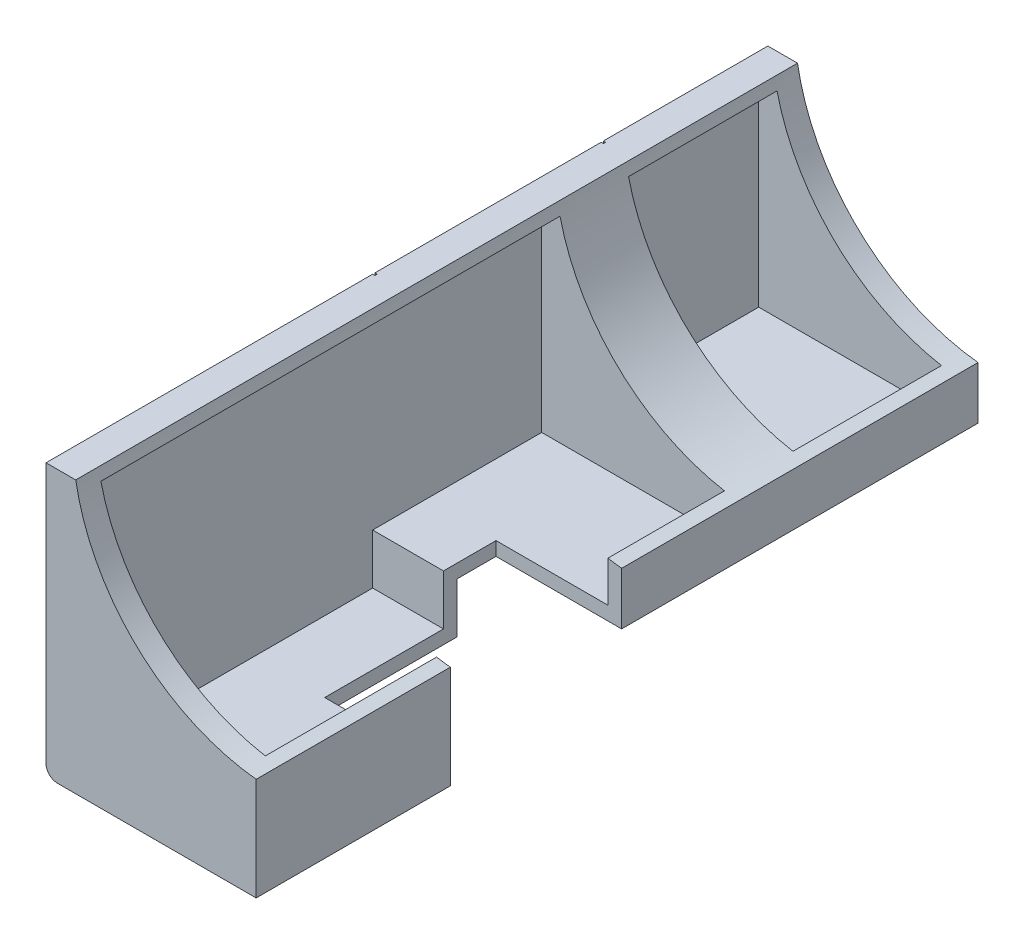
SolidWorks part; units mm, degrees
material "Acrylic (Medium-high impact)"
ref_plane "Front Plane" through (0, 0, 0) normal (0, 0, 1) x (1, 0, 0)
ref_plane "Top Plane" through (0, 0, 0) normal (0, 1, 0) x (1, 0, 0)
ref_plane "Right Plane" through (0, 0, 0) normal (1, 0, 0) x (0, 0, -1)
sketch "Sketch2" plane through (0, 0, 0) normal (0, 0, 1) x (1, 0, 0)
  line L0 (-0.9659, -13.448) -> (-0.9659, -8.948)
  line L1 (-8.8659, -1.548) -> (-10.1659, -1.548)
  line L2 (-10.1659, -1.548) -> (-10.1659, -13.448)
  line L3 (-10.1659, -13.448) -> (-0.9659, -13.448)
  arc A0 (-8.8659, -1.548) -> (-0.9659, -8.948) centre (0, 0) ccw
  dimension "D1" = 11.9
  dimension "D5" = 18
  dimension "D2" = 1.3
  dimension "D3" = 4.5
  dimension "D4" = 9.2
extrude "Boss-Extrude1" add sketch "Sketch2" against normal blind 31.6 contours L2 L3 L0 A0 L1
sketch "Sketch4" plane through (-10.1659, 0, 0) normal (-1, 0, 0) x (0, 0, 1)
  line L1 (-13.5, -12.248) -> (-0.8, -12.248)
  line L2 (-13.5, -12.248) -> (-13.5, -2.248)
  line L3 (-13.5, -2.248) -> (-0.8, -2.248)
  line L4 (-0.8, -12.248) -> (-0.8, -2.248)
  line L6 (-31.6, -1.548) -> (0, -1.548) construction
  line L8 (-23.5, -2.248) -> (-15.2, -2.248)
  line L9 (-23.5, -2.248) -> (-23.5, -10.048)
  line L10 (-23.5, -10.048) -> (-15.2, -10.048)
  line L11 (-15.2, -2.248) -> (-15.2, -10.048)
  line L12 (-31, -2.248) -> (-25.2, -2.248)
  line L13 (-31, -2.248) -> (-31, -9.848)
  line L14 (-31, -9.848) -> (-25.2, -9.848)
  line L15 (-25.2, -2.248) -> (-25.2, -9.848)
  line L16 (0, -1.548) -> (0, -13.448) construction
  dimension "D1" = 10
  dimension "D2" = 12.7
  dimension "D3" = 0.7
  dimension "D4" = 10.7
  dimension "D5" = 7.8
  dimension "D6" = 5.8
  dimension "D7" = 8.3
  dimension "D8" = 7.6
  dimension "D9" = 1.7
  dimension "D10" = 1.7
  dimension "D11" = 13.5
extrude "Boss-Extrude2" add sketch "Sketch4" along normal blind 0.35
fillet "Fillet1" radius 0.5 12 edges at (-10.3409, -10.048, -23.5) (-10.3409, -10.048, -15.2) (-10.3409, -2.248, -15.2) (-10.3409, -2.248, -23.5) (-10.3409, -12.248, -13.5) (-10.3409, -12.248, -0.8) (-10.3409, -2.248, -0.8) (-10.3409, -2.248, -13.5) (-10.3409, -9.848, -25.2) (-10.3409, -2.248, -31) (-10.3409, -9.848, -31) (-10.3409, -2.248, -25.2)
sketch "Sketch5" plane through (-10.5159, 0, 0) normal (-1, 0, 0) x (0, 0, 1)
  circle A0 centre (-13, -2.748) radius 0.25
  circle A1 centre (-1.3, -2.748) radius 0.25
  circle A2 centre (-23, -2.748) radius 0.25
  circle A3 centre (-23, -9.548) radius 0.25
  circle A4 centre (-1.3, -11.748) radius 0.25
  circle A5 centre (-13, -11.748) radius 0.25
  circle A6 centre (-15.7, -2.748) radius 0.25
  circle A7 centre (-15.7, -9.548) radius 0.25
  circle A8 centre (-30.5, -2.748) radius 0.25
  circle A9 centre (-25.7, -2.748) radius 0.25
  circle A10 centre (-25.7, -9.348) radius 0.25
  circle A11 centre (-30.5, -9.348) radius 0.25
  dimension "D1" = 0.5
extrude "Boss-Extrude3" add sketch "Sketch5" along normal blind 0.1
sketch "Sketch19" plane through (-10.1659, 0, 0) normal (-1, 0, 0) x (0, 0, 1)
  line L0 (-31.6, -1.548) -> (0, -1.548) construction
  line L1 (-31.6, -13.448) -> (-14.3, -13.448)
  line L2 (-31.6, -13.448) -> (-31.6, -11.248)
  line L3 (-31.6, -11.248) -> (-14.3, -11.248)
  line L4 (-14.3, -13.448) -> (-14.3, -11.248)
  line L5 (0, -1.548) -> (0, -13.448) construction
  dimension "D1" = 9.7
  dimension "D2" = 14.3
extrude "Cut-Extrude11" cut sketch "Sketch19" against normal through all
fillet "Fillet2" radius 0.5 2 edges at (-10.1659, -11.248, -22.95) (-10.1659, -13.448, -7.15)
sketch "Sketch21" plane through (-10.1659, 0, 0) normal (-1, 0, 0) x (0, 0, 1)
  line L0 (-31.6, -1.548) -> (0, -1.548) construction
  line L1 (-14.3, -11.248) -> (-14.4, -11.248)
  line L2 (-14.3, -11.248) -> (-14.3, -1.548)
  line L3 (-14.3, -1.548) -> (-14.4, -1.548)
  line L4 (-14.4, -11.248) -> (-14.4, -1.548)
  line L5 (-14.3, -11.248) -> (-31.6, -11.248) construction
  line L6 (-24.35, -1.548) -> (-24.35, -11.248) construction
  line L7 (-25.2, -9.348) -> (-25.2, -2.748) construction
  line L8 (-23.5, -2.748) -> (-23.5, -9.548) construction
  line L10 (-24.3, -11.248) -> (-24.4, -11.248)
  line L11 (-24.3, -11.248) -> (-24.3, -1.548)
  line L12 (-24.3, -1.548) -> (-24.4, -1.548)
  line L13 (-24.4, -11.248) -> (-24.4, -1.548)
  dimension "D1" = 0.1
  dimension "D2" = 0.1
extrude "Cut-Extrude13" cut sketch "Sketch21" against normal blind 0.1
sketch "Sketch20" plane through (0, 0, 0) normal (0, 1, 0) x (1, 0, 0)
  line L0 (-0.9659, 31.6) -> (-0.9659, 0) construction
  line L1 (-0.9659, 8.5) -> (-6.4659, 8.5)
  line L2 (-0.9659, 8.5) -> (-0.9659, 16)
  line L3 (-0.9659, 16) -> (-6.4659, 16)
  line L4 (-6.4659, 8.5) -> (-6.4659, 16)
  line L5 (-8.8659, 0) -> (-0.9659, 0) construction
  line L6 (-10.5159, 1.3) -> (-10.5159, 13) construction
  dimension "D1" = 7.5
  dimension "D2" = 8.5
  dimension "D3" = 4.05
  dimension "D4" = 5.5
extrude "Cut-Extrude12" cut sketch "Sketch20" against normal through all
sketch "Sketch22" plane through (0, -1.548, 0) normal (0, 1, 0) x (1, 0, 0)
  line L0 (-8.8659, 31.6) -> (-8.8659, 0) construction
  line L1 (-8.8659, 1) -> (-1.5659, 1)
  line L2 (-8.8659, 1) -> (-8.8659, 21.1)
  line L3 (-8.8659, 13.7) -> (-1.5659, 13.7)
  line L4 (-1.5659, 1) -> (-1.5659, 21.1)
  line L5 (-6.4659, 14.3) -> (-9.6659, 14.3) construction
  line L6 (-8.8659, 21.1) -> (-1.5659, 21.1)
  line L8 (-8.8659, 0) -> (-0.9659, 0) construction
  line L9 (-1.5659, 24.1) -> (-8.8659, 24.1)
  line L10 (-1.5659, 24.1) -> (-1.5659, 30.6)
  line L11 (-1.5659, 30.6) -> (-8.8659, 30.6)
  line L12 (-8.8659, 24.1) -> (-8.8659, 30.6)
  line L13 (-0.9659, 31.6) -> (-8.8659, 31.6) construction
  line L14 (-0.9659, 31.6) -> (-0.9659, 16) construction
  line M9 (-8.8659, 0) -> (-8.8659, 31.6)
  dimension "D1" = 1
  dimension "D2" = 1
  dimension "D3" = 0.6
  dimension "D4" = 6.5
  dimension "D5" = 3
  dimension "D6" = 0.6
extrude "Cut-Extrude14" cut sketch "Sketch22" against normal offset from surface (11.3 mm away) 0.6 contours L1 L4 L3 M9 region at (-5.2159, -1.548, -7.35) up to face at (-5.6992, -13.448, -7.6)
extrude "Cut-Extrude15" cut sketch "Sketch22<3>" against normal offset from surface (9.1 mm away) 0.6 contours L6 L2 L3 L4 | L10 L11 L9 M9 region at (-5.2159, -1.548, -27.35) region at (-5.2159, -1.548, -17.4) up to face at (-5.6992, -11.248, -20.6333)
sketch "Sketch22<3>" plane through (0, -1.548, 0) normal (0, 1, 0) x (1, 0, 0) same geometry as "Sketch22"
sketch "Sketch23" plane through (-8.8659, 0, 0) normal (1, 0, 0) x (0, 0, -1)
  line L0 (1, -12.848) -> (13.7, -12.848) construction
  line L1 (13.7, -12.848) -> (13.7, -10.648) construction
  line L2 (13.7, -10.648) -> (21.1, -10.648) construction
  line L3 (21.1, -10.648) -> (21.1, -1.548) construction
  line L5 (1, -1.548) -> (1, -12.848) construction
  line L6 (30.6, -10.648) -> (30.6, -1.548) construction
  line L8 (24.1, -1.548) -> (24.1, -10.648) construction
  line L9 (24.1, -10.648) -> (30.6, -10.648) construction
  line L10 (1, -12.848) -> (13.7, -12.848)
  line L11 (13.7, -12.848) -> (13.7, -10.648)
  line L12 (13.7, -10.648) -> (21.1, -10.648)
  line L13 (21.1, -10.648) -> (21.1, -2.048)
  line L14 (21.1, -2.048) -> (1, -2.048)
  line L15 (1, -2.048) -> (1, -12.848)
  line L16 (30.6, -10.648) -> (30.6, -2.048)
  line L17 (30.6, -2.048) -> (24.1, -2.048)
  line L18 (24.1, -2.048) -> (24.1, -10.648)
  line L19 (24.1, -10.648) -> (30.6, -10.648)
  line L22 (1, -1.548) -> (21.1, -1.548) construction
  dimension "D1" = 0.5
extrude "Cut-Extrude16" cut sketch "Sketch23" against normal offset from surface (0.7 mm away) 0.6 up to face at (-10.1659, -7.248, -7.15)
sketch "Sketch24" plane through (0, 0, -1) normal (0, 0, -1) x (-1, 0, 0)
  line L0 (8.8659, -2.048) -> (8.8659, -1.548) construction
  line L1 (8.8659, -2.048) -> (8.8659, -1.548)
  line L2 (8.8659, -2.048) -> (8.7639, -2.048)
  arc A0 (1.5659, -8.8627) -> (8.8659, -1.548) centre (0, 0) ccw construction
  arc A1 (8.7639, -2.048) -> (8.8659, -1.548) centre (0, 0) ccw
extrude "Boss-Extrude4" add sketch "Sketch24" along normal through all
